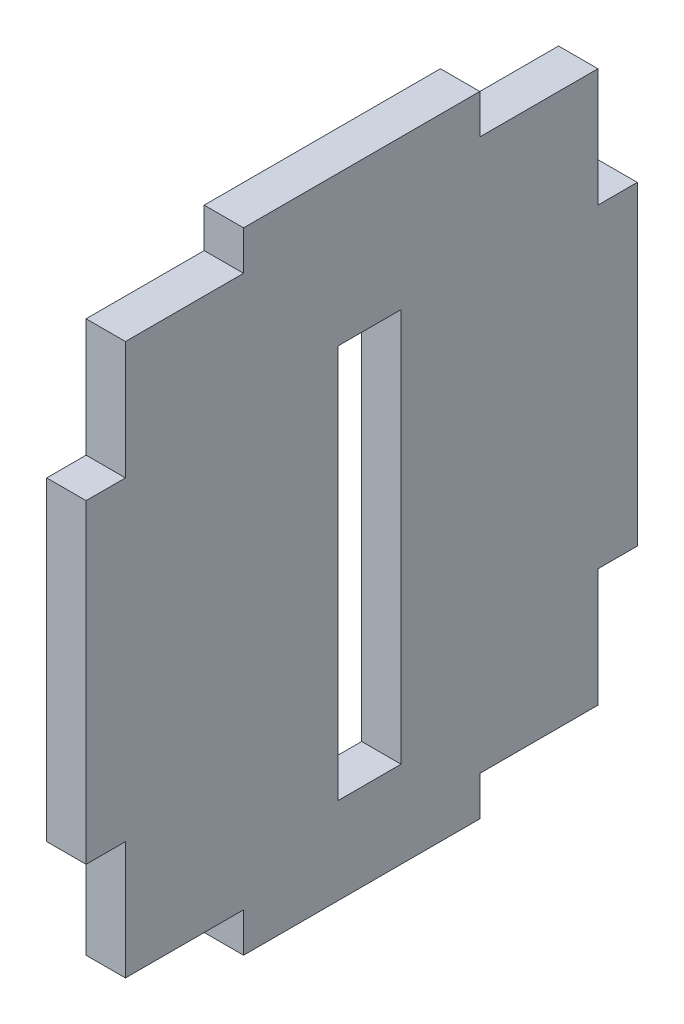
SolidWorks part; units mm, degrees
material "Acrylic (Medium-high impact)"
ref_plane "Front Plane" through (0, 0, 0) normal (0, 0, 1) x (1, 0, 0)
ref_plane "Top Plane" through (0, 0, 0) normal (0, 1, 0) x (1, 0, 0)
ref_plane "Right Plane" through (0, 0, 0) normal (1, 0, 0) x (0, 0, -1)
sketch "Sketch1" plane through (0, 0, 0) normal (1, 0, 0) x (0, 0, -1)
  line L1 (-35, -40) -> (35, -40)
  line L2 (-35, -40) -> (-35, 40)
  line L3 (-35, 40) -> (35, 40)
  line L4 (35, -40) -> (35, 40)
  line L5 (-35, -40) -> (35, 40) construction
  line L6 (-35, 40) -> (35, -40) construction
  point P0 (0, 0)
  dimension "D1" = 70
  dimension "D2" = 80
extrude "Boss-Extrude1" add sketch "Sketch1" along normal blind 5
sketch "Sketch3" plane through (5, 0, 0) normal (1, 0, 0) x (0, 0, -1)
  line L0 (-35, 20) -> (-30, 20)
  line L1 (-35, 40) -> (-35, -40) construction
  line L2 (-30, 20) -> (-30, 35)
  line L3 (-30, 35) -> (-15, 35)
  line L4 (-15, 35) -> (-15, 40)
  line L5 (35, 40) -> (-35, 40) construction
  line L6 (-15, 40) -> (-35, 40)
  line L7 (-35, 40) -> (-35, 20)
  dimension "D1" = 20
  dimension "D2" = 5
extrude "Cut-Extrude1" cut sketch "Sketch3" against normal through all both and the other way through all
mirror "Mirror1" about plane through (0, 0, 0) normal (0, 0, 1) of "Cut-Extrude1" second plane through (0, 0, 0) second plane normal (0, 1, 0)
sketch "Sketch4" plane through (5, 0, 0) normal (1, 0, 0) x (0, 0, -1)
  line L0 (35, -20) -> (35, 20) construction
  line L1 (-3, -28.9881) -> (5, -28.9881)
  line L2 (-3, -28.9881) -> (-3, 21.0119)
  line L3 (-3, 21.0119) -> (5, 21.0119)
  line L4 (5, -28.9881) -> (5, 21.0119)
  dimension "D1" = 8
  dimension "D2" = 50
  dimension "D3" = 30
extrude "Cut-Extrude2" cut sketch "Sketch4" against normal through all both
